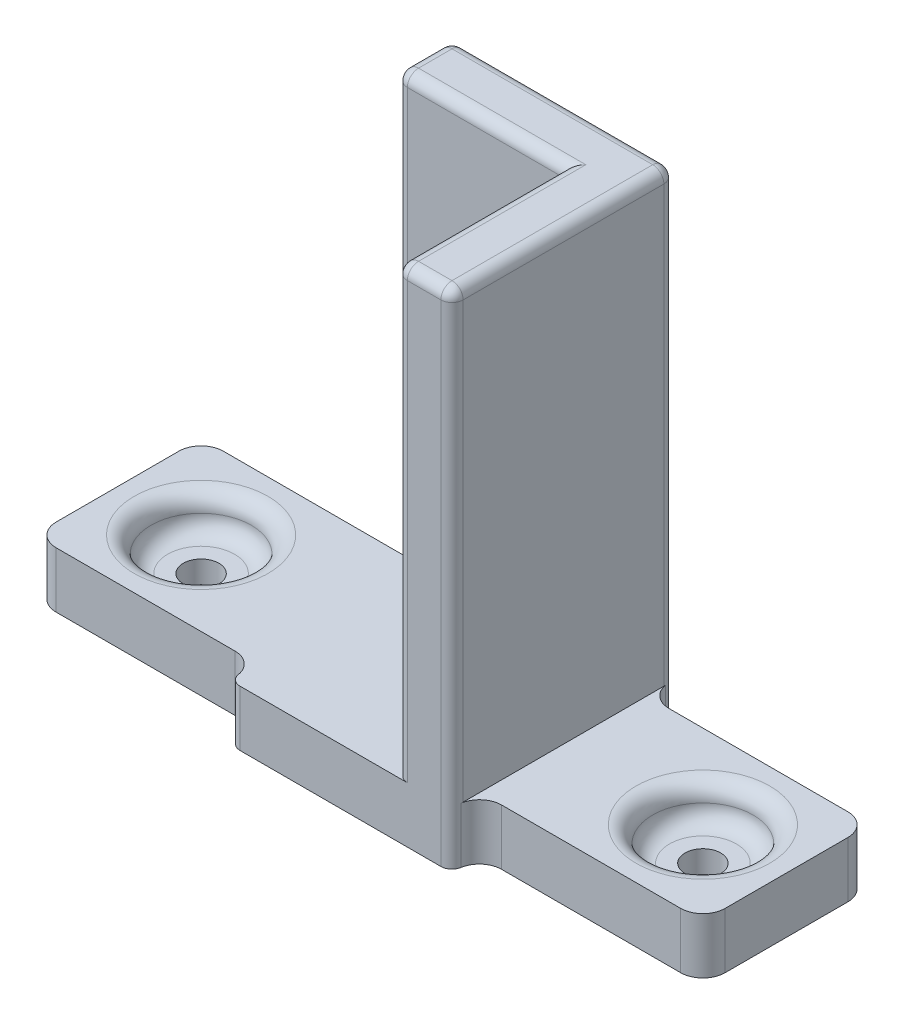
SolidWorks part; units mm, degrees
ref_plane "Front Plane" through (0, 0, 0) normal (0, 0, 1) x (1, 0, 0)
ref_plane "Top Plane" through (0, 0, 0) normal (0, 1, 0) x (1, 0, 0)
ref_plane "Right Plane" through (0, 0, 0) normal (1, 0, 0) x (0, 0, -1)
sketch "Sketch1" plane through (0, 0, 0) normal (0, 1, 0) x (1, 0, 0)
  line L1 (0, 0) -> (20, 0)
  line L2 (0, 0) -> (0, 20)
  line L3 (0, 20) -> (20, 20)
  line L4 (20, 0) -> (20, 20)
  dimension "D1" = 20
  dimension "D2" = 20
extrude "Boss-Extrude1" add sketch "Sketch1" along normal blind 5
sketch "Sketch2" plane through (0, 5, 0) normal (0, 1, 0) x (1, 0, 0)
  line L0 (0, 20) -> (20, 20)
  line L1 (20, 20) -> (20, 0)
  line L2 (20, 0) -> (15, 0)
  line L3 (0, 0) -> (20, 0) construction
  line L4 (15, 0) -> (15, 15)
  line L5 (15, 15) -> (0, 15)
  line L6 (0, 20) -> (0, 0) construction
  line L7 (0, 15) -> (0, 20)
  dimension "D1" = 15
  dimension "D2" = 15
extrude "Boss-Extrude2" add sketch "Sketch2" along normal blind 40
fillet "Fillet1" radius 1 3 edges at (0, 25, -15) (15, 25, 0) (0, 2.5, 0)
fillet "Fillet2" radius 1 3 edges at (20, 22.5, -20) (0, 22.5, -20) (20, 22.5, 0)
sketch "Sketch3" plane through (0, 5, 0) normal (0, 1, 0) x (1, 0, 0)
  line L0 (15, 15) -> (15, 1) construction
  line L1 (1, 15) -> (15, 15) construction
  circle A0 centre (10, 10) radius 2.5
  dimension "D1" = 5
  dimension "D3" = 5
  dimension "D2" = 5
extrude "Cut-Extrude1" cut sketch "Sketch3" against normal blind 3.2
sketch "Sketch4" plane through (0, 0, -15) normal (0, 0, 1) x (1, 0, 0)
  line L0 (15, 45) -> (15, 5) construction
  line L1 (1, 5) -> (15, 5) construction
  circle A0 centre (10, 15) radius 2.5
  circle A1 centre (10, 35) radius 2.5
  dimension "D1" = 5
  dimension "D4" = 5
  dimension "D2" = 10
  dimension "D3" = 20
extrude "Cut-Extrude2" cut sketch "Sketch4" against normal blind 3.2
sketch "Sketch5" plane through (15, 0, 0) normal (-1, 0, 0) x (0, 0, 1)
  line L0 (-15, 45) -> (-15, 5) construction
  line L1 (-15, 5) -> (-1, 5) construction
  circle A0 centre (-10, 15) radius 2.5
  circle A1 centre (-10, 35) radius 2.5
  dimension "D1" = 5
  dimension "D4" = 5
  dimension "D2" = 10
  dimension "D3" = 20
extrude "Cut-Extrude3" cut sketch "Sketch5" against normal blind 3.2
fillet "Fillet3" radius 0.5 5 edges at (10, 5, -7.5) (15, 15, -7.5) (15, 35, -7.5) (12.5, 35, -15) (12.5, 15, -15)
fillet "Fillet4" radius 1 11 edges at (15, 45, -8) (15.2929, 45, -0.2929) (17.5, 45, 0) (19.7071, 45, -0.2929) (20, 45, -10) (19.7071, 45, -19.7071) (10, 45, -20) (0.2929, 45, -19.7071) (0, 45, -17.5) (0.2929, 45, -15.2929) (8, 45, -15)
sketch "Sketch6" plane through (0, 0, 0) normal (0, 1, 0) x (1, 0, 0)
  line L0 (0, 19) -> (0, 1) construction
  line L1 (0, 17.5) -> (-20, 17.5)
  line L2 (0, 17.5) -> (0, 2.5)
  line L3 (0, 2.5) -> (-20, 2.5)
  line L4 (-20, 17.5) -> (-20, 2.5)
  line L5 (20, 1) -> (20, 19) construction
  line L6 (20, 2.5) -> (40, 2.5)
  line L7 (20, 2.5) -> (20, 17.5)
  line L8 (20, 17.5) -> (40, 17.5)
  line L9 (40, 2.5) -> (40, 17.5)
  dimension "D1" = 15
  dimension "D2" = 2.5
  dimension "D3" = 60
extrude "Boss-Extrude3" add sketch "Sketch6" along normal up to surface (5 mm away) up to face at (10, 5, -13)
fillet "Fillet5" radius 2 4 edges at (0, 2.5, -17.5) (20, 2.5, -17.5) (20, 2.5, -2.5) (0, 2.5, -2.5)
fillet "Fillet6" radius 2 4 edges at (40, 2.5, -2.5) (40, 2.5, -17.5) (-20, 2.5, -2.5) (-20, 2.5, -17.5)
sketch "Sketch7" plane through (0, 5, 0) normal (0, 1, 0) x (1, 0, 0)
  line L0 (-20, 4.5) -> (-20, 15.5) construction
  line L1 (40, 15.5) -> (40, 4.5) construction
  circle A0 centre (-12.5, 10) radius 4.5
  circle A1 centre (32.5, 10) radius 4.5
  point P7 (-20, 10)
  dimension "D1" = 9
  dimension "D2" = 7.5
  dimension "D3" = 7.5
extrude "Cut-Extrude4" cut sketch "Sketch7" against normal blind 3
fillet "Fillet7" radius 1.5 4 edges at (32.5, 2, -5.5) (-12.5, 2, -5.5) (32.5, 5, -5.5) (-12.5, 5, -5.5)
sketch "Sketch8" plane through (0, 2, 0) normal (0, 1, 0) x (1, 0, 0)
  circle A0 centre (-12.5, 10) radius 1.6
  circle A1 centre (32.5, 10) radius 1.6
  dimension "D1" = 3.2
extrude "Cut-Extrude5" cut sketch "Sketch8" against normal through all
